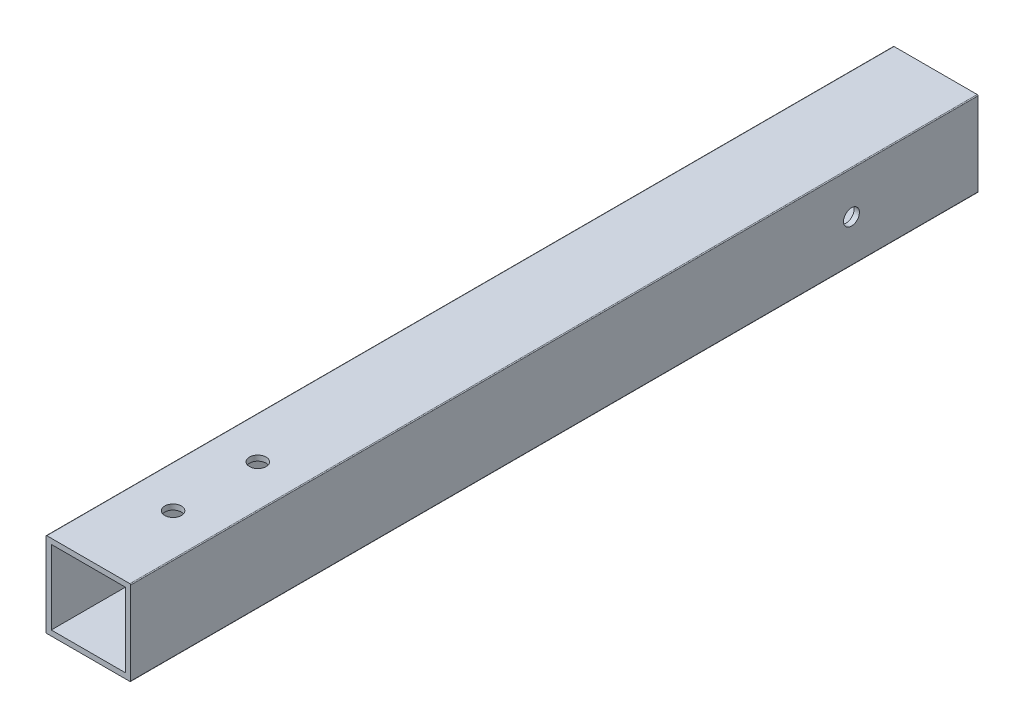
SolidWorks part; units mm, degrees
material "1060 Alloy"
ref_plane "Front Plane" through (0, 0, 0) normal (0, 0, 1) x (1, 0, 0)
ref_plane "Top Plane" through (0, 0, 0) normal (0, 1, 0) x (1, 0, 0)
ref_plane "Right Plane" through (0, 0, 0) normal (1, 0, 0) x (0, 0, -1)
ref_plane "Plane1" through (0, 0, 0) normal (0, 0, -1) x (-1, 0, 0)
sketch "Sketch1" plane through (0, 0, 0) normal (0, 0, -1) x (-1, 0, 0)
  line L4 (1.5875, -1.3335) -> (1.5875, 23.5585)
  line L5 (1.3335, 23.8125) -> (-23.5585, 23.8125)
  line L6 (-23.8125, 23.5585) -> (-23.8125, -1.3335)
  line L7 (-23.5585, -1.5875) -> (1.3335, -1.5875)
  line L9 (0, 22.225) -> (-22.225, 22.225)
  line L10 (0, 22.225) -> (0, 0)
  line L11 (0, 0) -> (-22.225, 0)
  line L12 (-22.225, 22.225) -> (-22.225, 0)
  line L13 (0, 22.225) -> (-22.225, 0) construction
  line L14 (0, 0) -> (-22.225, 22.225) construction
  arc A4 (1.3335, -1.5875) -> (1.5875, -1.3335) centre (1.3335, -1.3335) ccw
  arc A5 (1.5875, 23.5585) -> (1.3335, 23.8125) centre (1.3335, 23.5585) ccw
  arc A6 (-23.5585, 23.8125) -> (-23.8125, 23.5585) centre (-23.5585, 23.5585) ccw
  arc A7 (-23.8125, -1.3335) -> (-23.5585, -1.5875) centre (-23.5585, -1.3335) ccw
  point P24 (-11.1125, 11.1125)
  dimension "D1" = 25.4
  dimension "D2" = 25.4
  dimension "D3" = 1.5875
  dimension "D4" = 1.5875
  dimension "D5" = 1.5875
extrude "Boss-Extrude1" add sketch "Sketch1" against normal blind 254
sketch "Sketch2" plane through (-1.5875, 0, 0) normal (-1, 0, 0) x (0, 0, 1)
  line L0 (0, -1.3335) -> (0, 23.5585) construction
  line L1 (254, -1.3335) -> (0, -1.3335) construction
  line L2 (254, -1.3335) -> (254, 23.5585) construction
  circle A0 centre (12.6975, 11.3665) radius 1.5875
  circle A1 centre (241.3, 11.3665) radius 1.5875
  circle A2 centre (76.2, 11.3665) radius 6.35
  circle A3 centre (177.8, 11.3665) radius 6.35
  point P4 (0, 11.1125)
  dimension "D1" = 3.175
  dimension "D2" = 12.7
  dimension "D3" = 12.7
  dimension "D4" = 3.175
  dimension "D5" = 12.7
  dimension "D6" = 12.7
  dimension "D7" = 12.7
  dimension "D8" = 12.7
  dimension "D9" = 76.2
  dimension "D10" = 12.7
  dimension "D11" = 12.7
  dimension "D12" = 76.2
extrude "Cut-Extrude1" [suppressed] cut sketch "Sketch2" against normal through all
sketch "Sketch4" plane through (23.8125, 0, 0) normal (1, 0, 0) x (0, 0, -1)
  line L0 (-37.9333, 11.1125) -> (0, 11.1125) construction
  line L1 (0, 23.5585) -> (0, -1.3335) construction
  circle A2 centre (-37.9333, 11.1125) radius 2.3812
  dimension "D1" = 4.7625
  dimension "D2" = 37.9333
extrude "Cut-Extrude2" cut sketch "Sketch4" against normal through all contours A2
sketch "Sketch5" plane through (0, 23.8125, 0) normal (0, 1, 0) x (1, 0, 0)
  line L0 (11.1125, 0) -> (11.1125, -57.15) construction
  line L1 (-1.3335, 0) -> (23.5585, 0) construction
  circle A0 centre (11.1125, -57.15) radius 3.175
  dimension "D1" = 6.35
  dimension "D2" = 57.15
sketch "Sketch6" plane through (0, 23.8125, 0) normal (0, 1, 0) x (1, 0, 0)
  line L0 (11.1125, -254) -> (11.1125, -228.6) construction
  line L1 (-1.3335, -254) -> (23.5585, -254) construction
  line L2 (11.1125, -228.6) -> (11.1125, -203.2) construction
  line L3 (11.1125, -203.2) -> (8.8548, -202.1516) construction
  circle A0 centre (11.1125, -203.2) radius 2.4892
  circle A1 centre (11.1125, -228.6) radius 2.4892
  dimension "D3" = 4.9784
  dimension "D1" = 25.4
  dimension "D2" = 25.4
extrude "Cut-Extrude3" cut sketch "Sketch6" against normal blind 25.4
